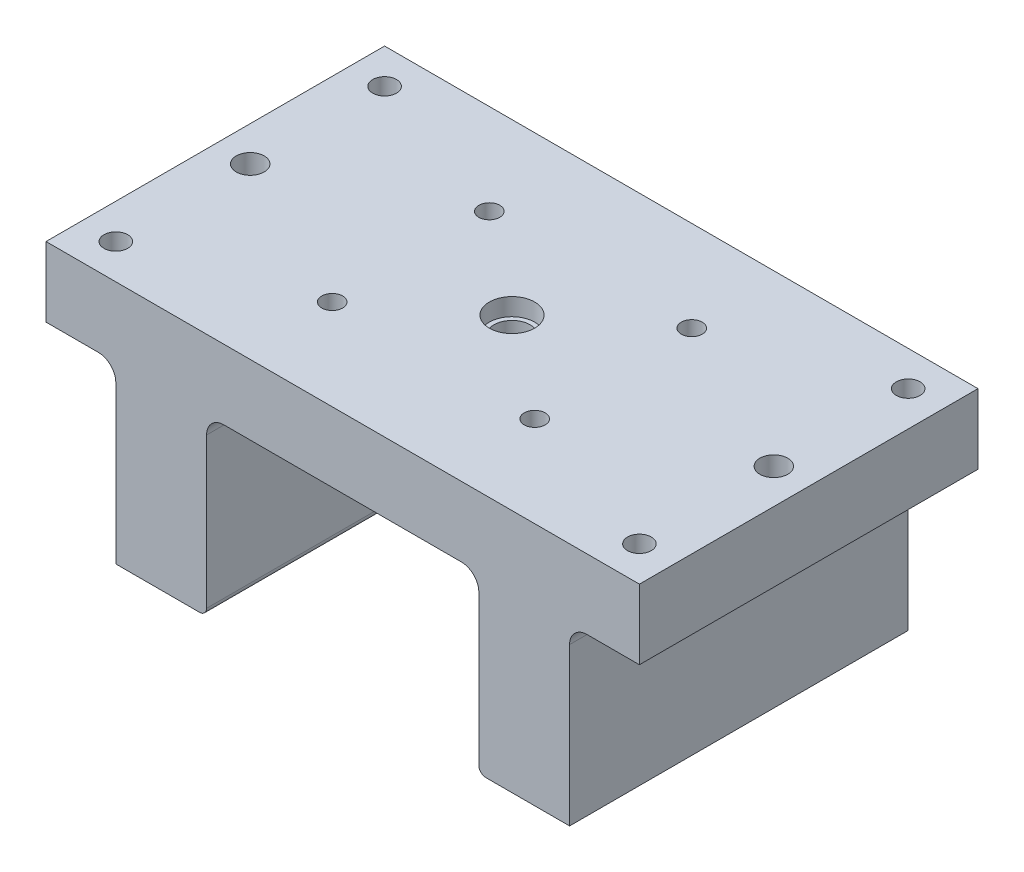
SolidWorks part; units mm, degrees
material "K110"
ref_plane "Front Plane" through (0, 0, 0) normal (0, 0, 1) x (1, 0, 0)
ref_plane "Top Plane" through (0, 0, 0) normal (0, 1, 0) x (1, 0, 0)
ref_plane "Right Plane" through (0, 0, 0) normal (1, 0, 0) x (0, 0, -1)
sketch "Sketch1" plane through (0, 0, 0) normal (0, 1, 0) x (1, 0, 0)
  line L0 (-65, -48.5) -> (-65, 48.5)
  line L7 (-65, 48.5) -> (65, 48.5)
  line L8 (65, -48.5) -> (65, 48.5)
  line L9 (-65, -48.5) -> (65, -48.5)
  point P0 (0, 0)
  point P10 (0, -48.5)
  point P11 (-65, 0)
  dimension "D3" = 97
  dimension "D4" = 130
extrude "Boss-Extrude1" add sketch "Sketch1" along normal blind 70
sketch "Sketch2" plane through (0, 0, 48.5) normal (0, 0, 1) x (1, 0, 0)
  line L0 (-65, 0) -> (65, 0) construction
  line L1 (-39, 0) -> (39, 0)
  line L2 (-39, 0) -> (-39, 50)
  line L3 (-39, 50) -> (39, 50)
  line L4 (39, 0) -> (39, 50)
  dimension "D1" = 78
  dimension "D2" = 50
extrude "Cut-Extrude1" cut sketch "Sketch2" against normal through all
fillet "Fillet3" radius 5 2 edges at (39, 50, 0) (-39, 50, 0)
sketch "Sketch3" plane through (0, 70, 0) normal (0, 1, 0) x (1, 0, 0)
  circle A0 centre (0, 0) radius 5.2
  dimension "D1" = 10.4
extrude "Cut-Extrude2" cut sketch "Sketch3" against normal through all
sketch "Sketch4" plane through (0, 70, 0) normal (0, 1, 0) x (1, 0, 0)
  circle A0 centre (0, 0) radius 6.5
  dimension "D1" = 13
extrude "Cut-Extrude3" cut sketch "Sketch4" against normal blind 5
fillet "Fillet4" radius 2 2 edges at (39, 0, 0) (-39, 0, 0)
hole_wizard "Ø5.0 (5) Diameter Hole1" positions "Sketch7" profile "Sketch6" hole size "Ø5.0" standard "ISO" end condition through all
sketch "Sketch7" plane through (0, 70, 0) normal (0, 1, 0) x (1, 0, 0)
  point P0 (-29, 22.5)
  point P3 (29, 22.5)
  point P6 (29, -22.5)
  point P9 (-29, -22.5)
sketch "Sketch6" plane through (-29, 70, -22.5) normal (1, 0, 0) x (0, 0, 1)
  line L0 (0, 0) -> (0, 70)
  line L1 (0, 70) -> (3, 70)
  line L2 (3, 70) -> (3, 0)
  line L5 (3, 0) -> (0, 0)
  line L11 (0, -6.35) -> (0, 107.95) construction
  dimension "Thru Hole Dia." = 6
  dimension "Thru Hole Depth" = 70
sketch "Sketch8" plane through (0, 70, 0) normal (0, 1, 0) x (1, 0, 0)
  line L0 (65, 48.5) -> (-65, 48.5) construction
  line L1 (-65, -48.5) -> (-85, -48.5)
  line L2 (-65, -48.5) -> (-65, 48.5)
  line L3 (-65, 48.5) -> (-85, 48.5)
  line L4 (-85, -48.5) -> (-85, 48.5)
  dimension "D1" = 20
extrude "Boss-Extrude2" add sketch "Sketch8" against normal blind 20
mirror "Mirror1" about plane through (0, 0, 0) normal (1, 0, 0) of "Boss-Extrude2"
fillet "Fillet5" radius 5 2 edges at (65, 50, 0) (-65, 50, 0)
hole_wizard "M8 Tapped Hole1" positions "Sketch11" profile "Sketch10" tap size "M8" standard "ISO" end condition through all
sketch "Sketch11" plane through (0, 70, 0) normal (0, 1, 0) x (1, 0, 0)
  line L0 (-85, 48.5) -> (-85, -48.5) construction
  line L1 (85, 48.5) -> (-85, 48.5) construction
  line L2 (-85, -48.5) -> (85, -48.5) construction
  line L3 (85, 48.5) -> (85, -48.5) construction
  point P0 (-75, 38.5)
  point P2 (-75, -38.5)
  point P4 (75, -38.5)
  point P6 (75, 38.5)
  dimension "D1" = 10
  dimension "D2" = 10
  dimension "D3" = 10
  dimension "D4" = 10
sketch "Sketch10" plane through (-75, 70, -38.5) normal (1, 0, 0) x (0, 0, 1)
  line L0 (0, 0) -> (0, 70)
  line L1 (0, 70) -> (3.4, 70)
  line L2 (3.4, 70) -> (3.4, 0)
  line L5 (3.4, 0) -> (0, 0)
  line L11 (0, -6.35) -> (0, 107.95) construction
  dimension "Thru Tap Drill Dia." = 6.8
  dimension "Thru Tap Drill Depth" = 70
cosmetic thread "Hole Thread1"
cosmetic thread "Hole Thread2"
cosmetic thread "Hole Thread3"
cosmetic thread "Hole Thread4"
hole_wizard "Ø8.0mm Dowel Hole1" positions "Sketch14" profile "Sketch13" hole size "Ø8.0" standard "ISO" end condition through all
sketch "Sketch14" plane through (0, 70, 0) normal (0, 1, 0) x (1, 0, 0)
  line L0 (-75, 38.5) -> (-75, -38.5) construction
  line L2 (75, 38.5) -> (75, -38.5) construction
  point P0 (-75, 0)
  point P2 (75, 0)
sketch "Sketch13" plane through (-75, 70, 0) normal (1, 0, 0) x (0, 0, 1)
  line L0 (0, 0) -> (0, 70)
  line L1 (0, 70) -> (4, 70)
  line L2 (4, 70) -> (4, 0)
  line L5 (4, 0) -> (0, 0)
  line L11 (0, -6.35) -> (0, 107.95) construction
  dimension "Thru Hole Dia." = 8
  dimension "Thru Hole Depth" = 70
